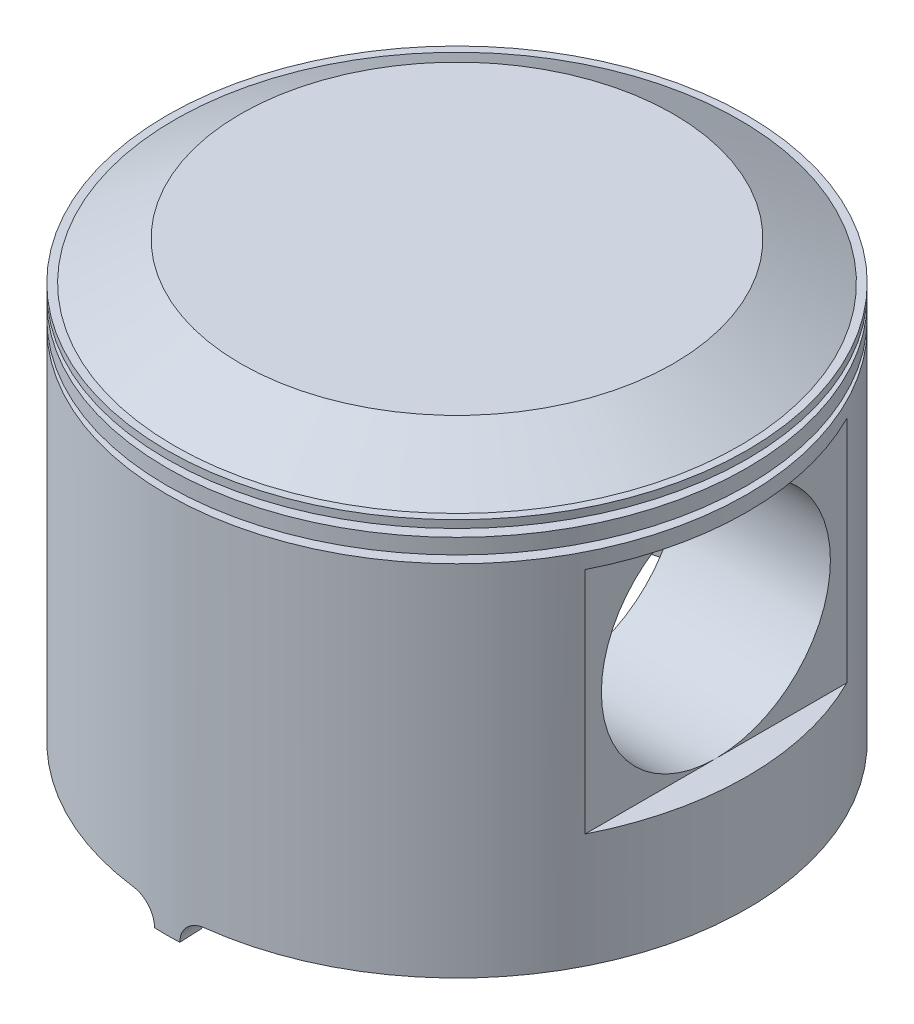
SolidWorks part; units mm, degrees
ref_plane "Front Plane" through (0, 0, 0) normal (0, 0, 1) x (1, 0, 0)
ref_plane "Top Plane" through (0, 0, 0) normal (0, 1, 0) x (1, 0, 0)
ref_plane "Right Plane" through (0, 0, 0) normal (1, 0, 0) x (0, 0, -1)
sketch "Piston CS" plane through (0, 0, 0) normal (0, 0, 1) x (1, 0, 0)
  line L0 (0, 0) -> (0, -5)
  line L1 (0, -5) -> (27, -5)
  line L2 (27, -5) -> (30, -6.7321)
  line L3 (30, -6.7321) -> (30, -16.7321)
  line L4 (30, -16.7321) -> (35, -16.7321)
  line L5 (35, -16.7321) -> (35, -57)
  line L6 (35, -57) -> (38, -57)
  line L8 (37, -5) -> (28.3397, 0)
  line L9 (28.3397, 0) -> (0, 0)
  line L10 (37, -5) -> (38, -5)
  line L12 (38, -5) -> (38, -57)
  dimension "Crown_Height" = 5
  dimension "D2" = 5
  dimension "D3" = 3
  dimension "D5" = 10
  dimension "D8" = 30
  dimension "D9" = 1
  dimension "Piston_Height" = 52
  dimension "Piston_Radius" = 38
  dimension "D7" = 5
  dimension "D1" = 5
revolve "Revolve1" add sketch "Piston CS" angle 360 about L0
sketch "Sketch5" plane through (0, -57, 0) normal (0, -1, 0) x (1, 0, 0)
  line L0 (0, -68.5184) -> (0, 57.0205) construction
  line L1 (-73.4461, 0) -> (71.8036, 0) construction
  line L2 (-24.1039, -38) -> (-24.1039, -18)
  line L3 (-24.1039, -18) -> (-14.1039, -18)
  line L4 (-14.1039, -18) -> (-14.1039, 18)
  line L5 (-24.1039, 18) -> (-14.1039, 18)
  line L6 (-24.1039, 38) -> (-24.1039, 18)
  line L7 (24.1039, 38) -> (24.1039, 18)
  line L8 (24.1039, 18) -> (14.1039, 18)
  line L9 (14.1039, -18) -> (14.1039, 18)
  line L10 (24.1039, -18) -> (14.1039, -18)
  line L11 (24.1039, -38) -> (24.1039, -18)
  arc A2 (-24.1039, 38) -> (-24.1039, -38) centre (0, 0) ccw
  arc A3 (24.1039, 38) -> (24.1039, -38) centre (0, 0) cw
  point P10 (-14.1039, 0)
  point P19 (14.1039, 0)
  dimension "D1" = 20
  dimension "D2" = 10
  dimension "D3" = 18
extrude "Boss-Extrude1" add sketch "Sketch5" against normal up to next
sketch "Gudgeon Hole" plane through (-14.1039, 0, 0) normal (1, 0, 0) x (0, 0, -1)
  line L0 (28.3397, 0) -> (-28.3397, 0) construction
  circle A0 centre (0, -27) radius 15
  dimension "Gudgeon_Diameter" = 30
  dimension "Gudgeon_Offset" = 27
extrude "Cut-Extrude1" cut sketch "Gudgeon Hole" against normal through all and the other way through all
ref_plane "Plane1" through (0, 0, 38) normal (0, 0, 1) x (1, 0, 0)
sketch "Gudgeon Hole Cutouts" plane through (0, 0, 38) normal (0, 0, 1) x (1, 0, 0)
  line L1 (-38, -42) -> (-38, -12) construction
  line L4 (33.9142, -12) -> (33.9142, -42)
  line L8 (-38, -12) -> (-33.9142, -12)
  line L9 (-33.9142, -12) -> (-33.9142, -42)
  line L11 (0, 0) -> (0, -52.5828) construction
  line L12 (28.3397, 0) -> (-28.3397, 0) construction
  line L15 (-33.9142, -42) -> (-38, -42)
  line L16 (-51.0412, -27) -> (-34.9142, -27) construction
  line L17 (33.9142, -42) -> (38, -42)
  line L18 (38, -12) -> (33.9142, -12)
  spline S0 degree 2 poles (-38, -12) (-32.0789, -27) (-38, -42) knots 0 0 0 1 1 1 weights 0.023 0.038 0.053 construction
  spline S1 degree 2 poles (-38, -12) (-32.0789, -27) (-38, -42) knots 0 0 0 1 1 1 weights 0.023 0.038 0.053
  spline S2 degree 2 poles (38, -42) (32.0789, -27) (38, -12) knots 0 0 0 1 1 1 weights 0.023 0.038 0.053 construction
  spline S3 degree 2 poles (38, -42) (32.0789, -27) (38, -12) knots 0 0 0 1 1 1 weights 0.023 0.038 0.053
  point P5 (-33.9142, -27)
  point P6 (-38, -27)
  dimension "D1" = 1
extrude "Cut-Extrude2" cut sketch "Gudgeon Hole Cutouts" against normal through all contours S1 L9 L8 | S3 L18 L4 L17 region at (-35.9571, -12.3028, 38)
sketch "Ring CS" plane through (0, 0, 0) normal (0, 0, 1) x (1, 0, 0)
  line L0 (37, -5) -> (38, -5) construction
  line L1 (38, -6) -> (36, -6)
  line L2 (38, -6) -> (38, -7)
  line L3 (38, -7) -> (36, -7)
  line L4 (36, -6) -> (36, -7)
  line L5 (38, -5) -> (38, -57) construction
  line L14 (38, -9) -> (36, -9)
  line L15 (38, -9) -> (38, -10)
  line L16 (38, -10) -> (36, -10)
  line L17 (36, -9) -> (36, -10)
  line L22 (38, -6) -> (38, -9) construction
  dimension "Groove_Offset" = 1
  dimension "Groove_Depth" = 2
  dimension "Groove_Height" = 1
  dimension "Groove_Spacing" = 3
  dimension "Num_Grooves" = 2
revolve "Cut-Revolve1" cut sketch "Ring CS" angle 360 about L0
sketch "Sketch9" plane through (0, -57, 0) normal (0, -1, 0) x (1, 0, 0)
  line L0 (0, 54.5291) -> (0, -35) construction
  line L1 (-49.8964, 0) -> (45, 0) construction
  line L2 (-1.5267, 34.9667) -> (-1.6575, 37.9638)
  line L3 (1.5267, 34.9667) -> (1.6575, 37.9638)
  line L4 (1.5267, 34.9667) -> (1.6575, 37.9638) construction
  line L5 (-1.5267, 34.9667) -> (-1.6575, 37.9638) construction
  line L6 (1.5267, -34.9667) -> (1.6575, -37.9638) construction
  line L7 (-1.5267, -34.9667) -> (-1.6575, -37.9638) construction
  line L8 (1.5267, -34.9667) -> (1.6575, -37.9638)
  line L9 (-1.5267, -34.9667) -> (-1.6575, -37.9638)
  line L10 (0, 35) -> (0, -38) construction
  circle A0 centre (0, 0) radius 35 construction
  circle A1 centre (0, 0) radius 35 construction
  circle A2 centre (0, 0) radius 38 construction
  arc A3 (-1.5267, -34.9667) -> (1.5267, -34.9667) centre (0, 0) ccw
  arc A4 (1.5267, 34.9667) -> (-1.5267, 34.9667) centre (0, 0) ccw
  arc A5 (-1.6575, -37.9638) -> (1.6575, -37.9638) centre (0, 0) ccw
  arc A6 (1.6575, 37.9638) -> (-1.6575, 37.9638) centre (0, 0) ccw
  dimension "D1" = 2.5
  dimension "D2" = 5
extrude "Boss-Extrude2" add sketch "Sketch9" along normal blind 3
fillet "Fillet1" radius 3 4 edges at (-1.5921, -57, 36.4653) (1.5921, -57, 36.4653) (-1.5921, -57, -36.4653) (1.5921, -57, -36.4653)
equation "\"Crown_Height@Piston CS\"=5"
equation "\"Groove_Spacing@Ring CS\"=3"
equation "\"Gudgeon_Offset@Gudgeon Hole\"= ( \"Gudgeon_Diameter@Gudgeon Hole\" / 2 ) + \"Crown_Height@Piston CS\" + \"Groove_Offset@Ring CS\" + ( \"Groove_Spacing@Ring CS\" * \"Num_Grooves@Ring CS\" )"
equation "\"Gudgeon_Diameter@Gudgeon Hole\"     = 30"
equation "\"Groove_Height@Ring CS\"=1"
equation "\"Groove_Offset@Ring CS\"=1"
equation "\"Groove_Depth@Ring CS\"=2"
equation "\"Piston_Height@Piston CS\"= \"Gudgeon_Offset@Gudgeon Hole\" + ( \"Gudgeon_Diameter@Gudgeon Hole\" / 2 ) + 10"
equation "\"Piston_Radius@Piston CS\"     = 38"
